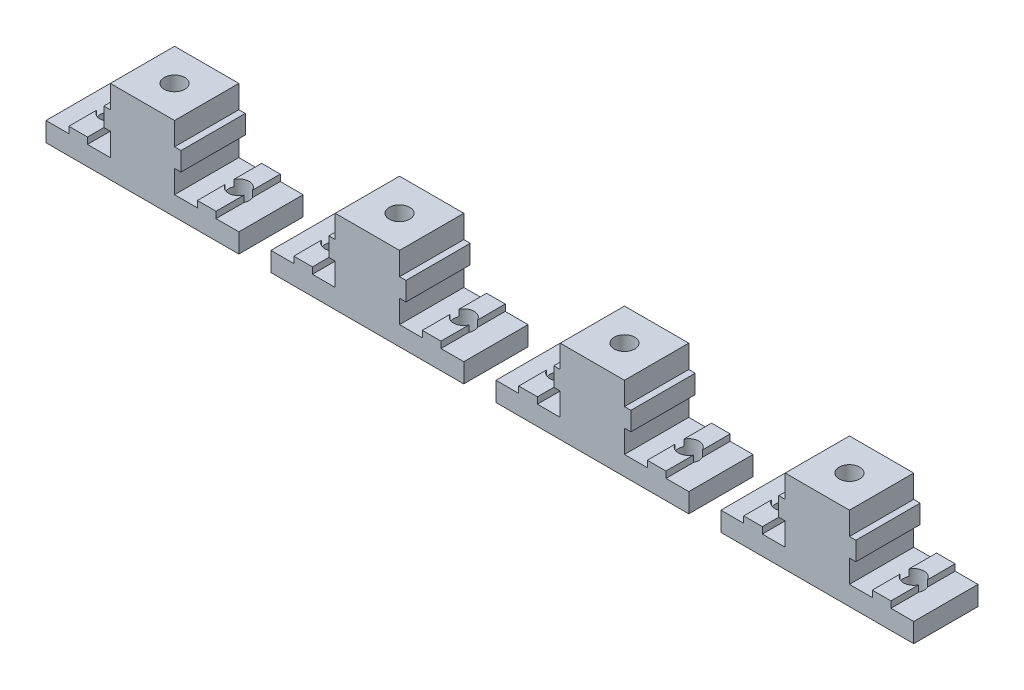
SolidWorks part; units mm, degrees
ref_plane "Front Plane" through (0, 0, 0) normal (0, 0, 1) x (1, 0, 0)
ref_plane "Top Plane" through (0, 0, 0) normal (0, 1, 0) x (1, 0, 0)
ref_plane "Right Plane" through (0, 0, 0) normal (1, 0, 0) x (0, 0, -1)
sketch "Esquisse1" plane through (0, 0, 0) normal (0, 0, 1) x (1, 0, 0)
  line L0 (-15, 0) -> (-15, 3)
  line L1 (-15, 3) -> (-11.45, 3)
  line L2 (-11.45, 3) -> (-11.45, 4)
  line L3 (-11.45, 4) -> (-8.55, 4)
  line L4 (-8.55, 4) -> (-8.55, 3)
  line L5 (-8.55, 3) -> (-5, 3)
  line L6 (-5, 3) -> (-5, 6.55)
  line L7 (0, 0) -> (-15, 0)
  line L8 (-5, 6.55) -> (-6, 6.55)
  line L9 (-6, 6.55) -> (-6, 9.45)
  line L10 (-6, 9.45) -> (-5, 9.45)
  line L11 (-5, 9.45) -> (-5, 13)
  line L12 (-5, 13) -> (0, 13)
  line L13 (0, 13) -> (0, 0)
  dimension "D1" = 15
  dimension "D2" = 3
  dimension "D3" = 1
  dimension "D4" = 2.9
  dimension "D5" = 3.55
  dimension "D6" = 5
  dimension "D7" = 10
  dimension "D8" = 2.9
  dimension "D9" = 3.55
extrude "Main" add sketch "Esquisse1" along normal blind 10
sketch "Esquisse2" plane through (0, 4, 0) normal (0, 1, 0) x (1, 0, 0)
  line L2 (-11.45, -10) -> (-15, -10) construction
  line L4 (-8.55, 0) -> (-11.45, 0) construction
  circle A1 centre (-10, -5) radius 1.6
  point P12 (-10, 0)
  dimension "D2" = 5
  dimension "D3" = 3.2
  dimension "D1" = 5
extrude "TopHole" cut sketch "Esquisse2" against normal through all
ref_axis "Axe1" through (-5.5, 0, 0) along (1, 0, 0)
mirror "Symétrie1" about plane through (0, 0, 0) normal (1, 0, 0) of "Main", "TopHole"
sketch "Esquisse3" plane through (0, 13, 0) normal (0, 1, 0) x (1, 0, 0)
  line L0 (0, -2.2) -> (0, 2.2) construction
  line L2 (5, -10) -> (-5, -10) construction
  circle A1 centre (0, -5) radius 1.6
  dimension "D1" = 3.2
  dimension "D2" = 5
extrude "Enlèv. mat.-Extru.2" cut sketch "Esquisse3" against normal through all
ref_axis "Axe2" through (16.5, 0, 0) along (-1, 0, 0)
pattern_linear "Répétition linéaire3" count 4 spacing 35 along (1, 0, 0) of bodies 108
